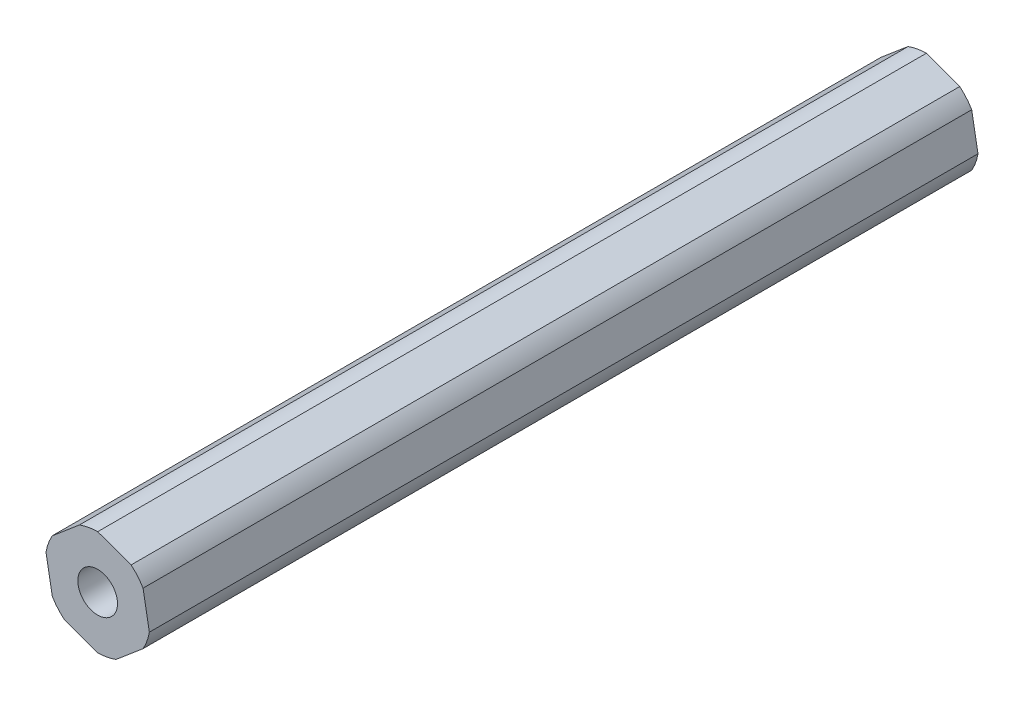
SolidWorks part; units mm, degrees
material "7075-T6 (SN)"
ref_plane "Front Plane" through (0, 0, 0) normal (0, 0, 1) x (1, 0, 0)
ref_plane "Top Plane" through (0, 0, 0) normal (0, 1, 0) x (1, 0, 0)
ref_plane "Right Plane" through (0, 0, 0) normal (1, 0, 0) x (0, 0, -1)
sketch "Sketch1" plane through (0, 0, 0) normal (0, 0, 1) x (1, 0, 0)
  line L1 (-6.6545, 1.1312) -> (-5.8457, -3.375)
  line L2 (-4.3069, -5.1974) -> (0, -6.75)
  line L3 (2.3476, -6.3286) -> (5.8457, -3.375)
  line L4 (6.6545, -1.1312) -> (5.8457, 3.375)
  line L5 (4.3069, 5.1974) -> (0, 6.75)
  line L6 (-2.3476, 6.3286) -> (-5.8457, 3.375)
  circle A0 centre (0, 0) radius 6.35 construction
  arc A1 (-5.8457, 3.375) -> (-6.6545, 1.1312) centre (0, 0) ccw
  arc A2 (-5.8457, -3.375) -> (-4.3069, -5.1974) centre (0, 0) ccw
  arc A3 (0, -6.75) -> (2.3476, -6.3286) centre (0, 0) ccw
  arc A4 (5.8457, -3.375) -> (6.6545, -1.1312) centre (0, 0) ccw
  arc A5 (5.8457, 3.375) -> (4.3069, 5.1974) centre (0, 0) ccw
  arc A6 (0, 6.75) -> (-2.3476, 6.3286) centre (0, 0) ccw
  dimension "D1" = 12.7
  dimension "D2" = 13.5
extrude "Boss-Extrude1" add sketch "Sketch1" along normal blind 106.7181
sketch "Sketch2" plane through (0, 0, 106.7181) normal (0, 0, 1) x (1, 0, 0)
  circle A0 centre (0, 0) radius 2.0193
  dimension "D1" = 4.0386
extrude "Cut-Extrude1" cut sketch "Sketch2" against normal through all
hole_wizard "1/4-20 Tapped Hole1" positions "Sketch5" profile "Sketch6" tap size "1/4-20" standard "ANSI Inch"
sketch "Sketch5" plane through (0, 0, 106.7181) normal (0, 0, 1) x (1, 0, 0)
  point P0 (0, 0)
sketch "Sketch6" plane through (0, 0, 106.7181) normal (1, 0, 0) x (0, -1, 0)
  line L0 (0, 0) -> (0, 20.5838)
  line L1 (0, 20.5838) -> (2.5527, 19.05)
  line L2 (2.5527, 19.05) -> (2.5527, 0)
  line L5 (2.5527, 0) -> (0, 0)
  line L10 (0, 20.5838) -> (-2.5527, 19.05) construction
  line L11 (0, -6.35) -> (0, 107.95) construction
  dimension "Tap Drill Dia." = 5.1054
  dimension "Tap Drill Depth" = 19.05
  dimension "Drill Angle" = 118
cosmetic thread "Hole Thread1" parameters "D1"=12.7, "D2"=6.35
hole_wizard "1/4-20 Tapped Hole2" positions "Sketch7" profile "Sketch8" tap size "1/4-20" standard "ANSI Inch"
sketch "Sketch7" plane through (0, 0, 0) normal (0, 0, -1) x (-1, 0, 0)
  point P0 (0, 0)
sketch "Sketch8" plane through (0, 0, 0) normal (1, 0, 0) x (0, 1, 0)
  line L0 (0, 0) -> (0, 20.5838)
  line L1 (0, 20.5838) -> (2.5527, 19.05)
  line L2 (2.5527, 19.05) -> (2.5527, 0)
  line L5 (2.5527, 0) -> (0, 0)
  line L10 (0, 20.5838) -> (-2.5527, 19.05) construction
  line L11 (0, -6.35) -> (0, 107.95) construction
  dimension "Tap Drill Dia." = 5.1054
  dimension "Tap Drill Depth" = 19.05
  dimension "Drill Angle" = 118
cosmetic thread "Hole Thread2" parameters "D1"=12.7, "D2"=6.35
